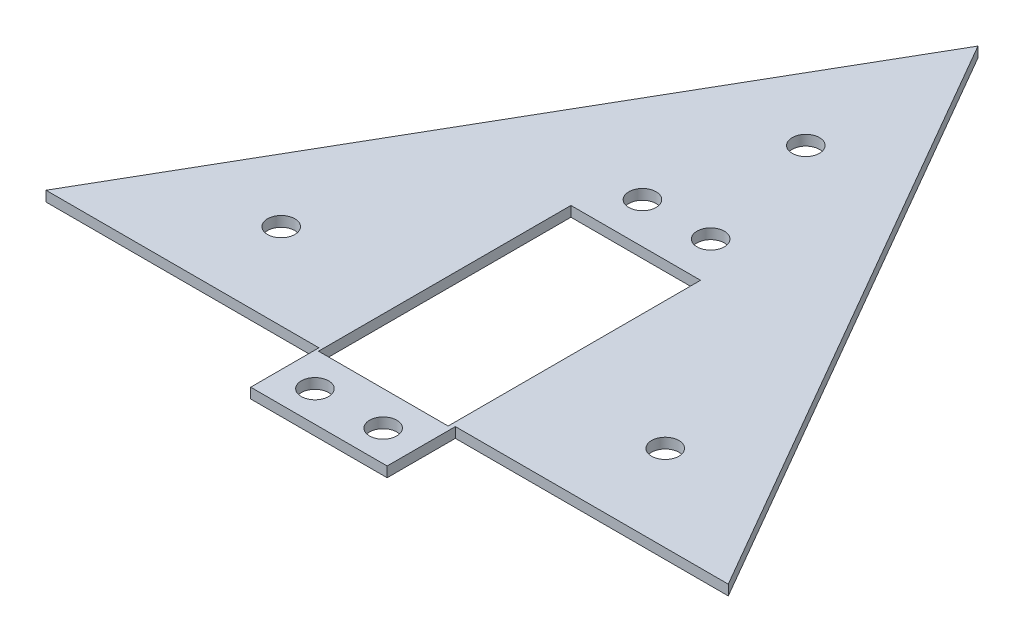
SolidWorks part; units mm, degrees
ref_plane "Front Plane" through (0, 0, 0) normal (0, 0, 1) x (1, 0, 0)
ref_plane "Top Plane" through (0, 0, 0) normal (0, 1, 0) x (1, 0, 0)
ref_plane "Right Plane" through (0, 0, 0) normal (1, 0, 0) x (0, 0, -1)
sketch "Sketch1" plane through (0, 0, 0) normal (0, 1, 0) x (1, 0, 0)
  line L1 (0, 57.735) -> (-50, -28.8675)
  line L2 (-50, -28.8675) -> (-10, -28.8675)
  line L3 (50, -28.8675) -> (0, 57.735)
  line L4 (-10, -28.8675) -> (-10, -38.8675)
  line L5 (-10, -38.8675) -> (10, -38.8675)
  line L6 (10, -38.8675) -> (10, -28.8675)
  line L7 (10, -28.8675) -> (50, -28.8675)
  circle A0 centre (0, 0) radius 28.8675 construction
  point P9 (0, -28.8675)
  dimension "D1" = 100
  dimension "D2" = 20
  dimension "D3" = 10
base flange "Base-Flange1" sketch "Sketch1" thickness 1.5 reverse thickness direction no parameters "D1"=0.1
sketch "Sketch6" plane through (0, 0, 0) normal (0, 1, 0) x (1, 0, 0)
  circle A0 centre (0, 32.5) radius 2
  circle A1 centre (28.1458, -16.25) radius 2
  circle A2 centre (-28.1458, -16.25) radius 2
  point P10 (0, 0)
  dimension "D1" = 32.5
  dimension "D2" = 3
extrude "Cut-Extrude1" cut sketch "Sketch6" against normal blind 10 normal cut yes
sketch "Sketch7" plane through (0, 0, 0) normal (0, 1, 0) x (1, 0, 0)
  line L0 (-10, -28.8675) -> (-10, -38.8675) construction
  line L1 (-10, -38.8675) -> (10, -38.8675) construction
  line L2 (-9.6, 7.6725) -> (9.4, 7.6725)
  line L3 (-9.6, 7.6725) -> (-9.6, -29.3275)
  line L4 (-9.6, -29.3275) -> (9.4, -29.3275)
  line L5 (9.4, 7.6725) -> (9.4, -29.3275)
  line L7 (-10, -28.8675) -> (-10, -38.8675) construction
  circle A0 centre (-5.1, -34.3475) radius 2
  circle A1 centre (4.9, -34.3475) radius 2
  circle A2 centre (-5.1, 13.6525) radius 2
  circle A3 centre (4.9, 13.6525) radius 2
  dimension "D1" = 10
  dimension "D2" = 4.9
  dimension "D4" = 37
  dimension "D5" = 19
  dimension "D6" = 48
  dimension "D7" = 4.52
  dimension "D8" = 4.52
  dimension "D9" = 0.4
  dimension "D10" = 5.02
  dimension "D3" = 2
extrude "Cut-Extrude2" cut sketch "Sketch7" against normal blind 10 normal cut yes
sketch "Bend-Lines1" [suppressed] plane through (0, 0, 0) normal (0, 1, 0) x (1, 0, 0)
sketch "Bounding-Box1" [suppressed] plane through (0, 0, 0) normal (0, 1, 0) x (1, 0, 0)
sheet metal parameters "Sheet-Metal1" thickness 1.5 parameters "D1"=0.1
flat pattern "Flat-Pattern1" [suppressed]
sketch "Bend-Lines2" plane through (0, 0, 0) normal (0, 1, 0) x (1, 0, 0)
sketch3d "Bounding-Box2" [suppressed]
  line L0 (-75, 14.4338, 0) -> (-25, -72.1688, 0) construction
  line L1 (0, 57.735, 0) -> (50, -28.8675, 0) construction
  line L2 (-75, 14.4338, 0) -> (0, 57.735, 0) construction
  line L3 (-25, -72.1688, 0) -> (50, -28.8675, 0) construction
sheet metal parameters "Sheet-Metal2" thickness 1.5 parameters "D1"=0.1
flat pattern "Flat-Pattern1"
sketch "Bend-Lines2" plane through (0, 0, 0) normal (0, 1, 0) x (1, 0, 0)
sketch3d "Bounding-Box2" [suppressed]
  line L0 (-75, 14.4338, 0) -> (-25, -72.1688, 0) construction
  line L1 (0, 57.735, 0) -> (50, -28.8675, 0) construction
  line L2 (-75, 14.4338, 0) -> (0, 57.735, 0) construction
  line L3 (-25, -72.1688, 0) -> (50, -28.8675, 0) construction
sheet metal parameters "Sheet-Metal3" thickness 1.5 parameters "D1"=0.1
flat pattern "Flat-Pattern1"
sketch "Bend-Lines2" plane through (0, 0, 0) normal (0, 1, 0) x (1, 0, 0)
sketch3d "Bounding-Box2" [suppressed]
  line L0 (-75, 14.4338, 0) -> (-25, -72.1688, 0) construction
  line L1 (0, 57.735, 0) -> (50, -28.8675, 0) construction
  line L2 (-75, 14.4338, 0) -> (0, 57.735, 0) construction
  line L3 (-25, -72.1688, 0) -> (50, -28.8675, 0) construction
